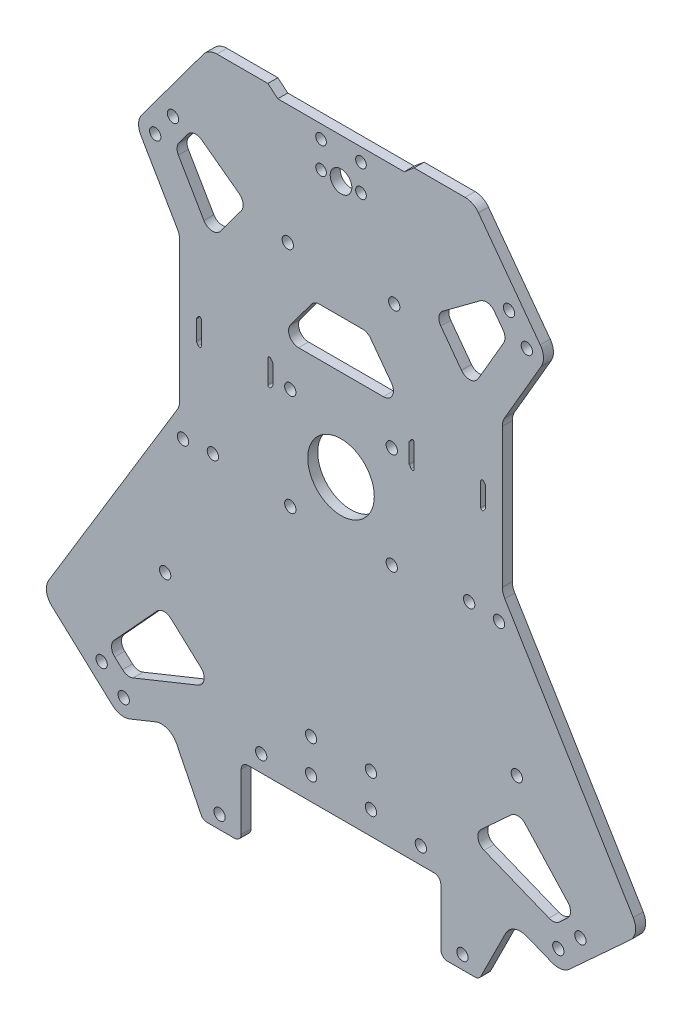
SolidWorks part; units mm, degrees
material "Thornel Mat VMA"
ref_plane "Front Plane" through (0, 0, 0) normal (0, 0, 1) x (1, 0, 0)
ref_plane "Top Plane" through (0, 0, 0) normal (0, 1, 0) x (1, 0, 0)
ref_plane "Right Plane" through (0, 0, 0) normal (1, 0, 0) x (0, 0, -1)
sketch "Sketch1" plane through (0, 0, 0) normal (0, 0, 1) x (1, 0, 0)
  line L0 (0, 0) -> (19, 0)
  line L1 (19, 0) -> (21.9794, 2.5)
  line L2 (21.9794, 2.5) -> (39.8216, 2.5)
  line L3 (39.8216, 2.5) -> (61.83, -27.2427)
  line L4 (61.83, -27.2427) -> (48.5, -50.146)
  line L5 (48.5, -50.146) -> (48.5, -94.8136)
  line L6 (48.5, -94.8136) -> (89.9615, -163.231)
  line L7 (89.9615, -163.231) -> (66.3721, -184.8537)
  line L8 (66.3721, -184.8537) -> (51.5362, -178.8624)
  line L9 (51.5362, -178.8624) -> (41.5, -199)
  line L10 (41.5, -199) -> (30, -199)
  line L11 (30, -199) -> (30, -178)
  line L12 (30, -178) -> (0, -178)
  line L14 (0, 0) -> (0, -178)
  circle A0 centre (6, -4) radius 1.6
  dimension "D20" = 3.2
  dimension "D2" = 2.5
  dimension "D3" = 140
  dimension "D4" = 113.3
  dimension "D5" = 126.5
  dimension "D6" = 37
  dimension "D7" = 30
  dimension "D8" = 26.5
  dimension "D9" = 41.5
  dimension "D10" = 48.5
  dimension "D11" = 80
  dimension "D12" = 178
  dimension "D13" = 32
  dimension "D14" = 115.5
  dimension "D15" = 16
  dimension "D16" = 94.5
  dimension "D17" = 22.5
  dimension "D18" = 116.491
  dimension "D19" = 21
  dimension "D21" = 19
  dimension "D22" = 4
  dimension "D23" = 6
extrude "Boss-Extrude1" add sketch "Sketch1" along normal blind 3 contours L14 L12 L11 L10 L9 L8 L7 L6 L5 L4 L3 L2 L1 L0
extrude "Cut-Extrude1" cut sketch "Sketch1<3>" along normal through all contours A0
sketch "Sketch1<3>" plane through (0, 0, 0) normal (0, 0, 1) x (1, 0, 0) same geometry as "Sketch1"
fillet "Fillet1" radius 5 7 edges at (39.8216, 2.5, 1.5) (51.5362, -178.8624, 1.5) (66.3721, -184.8537, 1.5) (89.9615, -163.231, 1.5) (48.5, -94.8136, 1.5) (48.5, -50.146, 1.5) (61.83, -27.2427, 1.5)
fillet "Fillet2" radius 2 3 edges at (30, -178, 1.5) (30, -199, 1.5) (41.5, -199, 1.5)
hole_wizard "M3 Clearance Hole2" positions "Sketch6" profile "Sketch7" hole size "M3" standard "ANSI Metric" end condition up to next
sketch "Sketch6" plane through (0, 0, 3) normal (0, 0, 1) x (1, 0, 0)
  line L0 (71.9537, -172.9547) -> (65.3192, -179.0361) construction
  line L2 (86.9389, -166.0016) -> (68.6977, -182.722) construction
  line L3 (71.9537, -172.9547) -> (77.851, -167.5491) construction
  line L7 (52.8498, -140.2738) -> (55.4731, -103.367) construction
  line L9 (52.8498, -140.2738) -> (77.851, -167.5491) construction
  line L11 (55.4731, -103.367) -> (47.4932, -102.7998) construction
  line L12 (47.4932, -102.7998) -> (38.5159, -102.1616) construction
  line L13 (47.4932, -102.7998) -> (51.7693, -100.2084) construction
  line L14 (49.2239, -96.0081) -> (87.8365, -159.7244) construction
  line L15 (50.5, -20.3369) -> (55.8534, -27.5716) construction
  line L17 (41.3207, 0.4741) -> (59.8727, -24.5975) construction
  line L18 (50.5, -20.3369) -> (45.7414, -13.9061) construction
  line L20 (45.7414, -13.9061) -> (15.9987, -35.9145) construction
  point P0 (65.3192, -179.0361)
  point P3 (71.9537, -172.9547)
  point P23 (52.8498, -140.2738)
  point P34 (47.4932, -102.7998)
  point P36 (38.5159, -102.1616)
  point P48 (55.8534, -27.5716)
  point P51 (50.5, -20.3369)
  point P66 (15.9987, -35.9145)
  dimension "D1" = 9
  dimension "D2" = 37
  dimension "D3" = 8
  dimension "D4" = 5
sketch "Sketch7" plane through (65.3192, -179.0361, 3) normal (1, 0, 0) x (0, -1, 0)
  line L0 (0, 0) -> (0, 3.001)
  line L1 (0, 3.001) -> (1.7, 3.001)
  line L2 (1.7, 3.001) -> (1.7, 0)
  line L5 (1.7, 0) -> (0, 0)
  line L11 (0, -6.35) -> (0, 107.95) construction
  dimension "Thru Hole Dia." = 3.4
  dimension "Thru Hole Depth" = 3.001
hole_wizard "M3 Clearance Hole3" positions "Sketch8" profile "Sketch9" hole size "M3" standard "ANSI Metric" end condition up to next
sketch "Sketch8" plane through (0, 0, 3) normal (0, 0, 1) x (1, 0, 0)
  line L0 (9, -171) -> (9, -178) construction
  line L1 (28, -178) -> (0, -178) construction
  line L3 (24, -173) -> (24, -178) construction
  line L5 (9, -171) -> (9, -161) construction
  line L6 (30, -197) -> (30, -180) construction
  line L7 (40.2621, -199) -> (32, -199) construction
  line L8 (0, 0) -> (0, -178) construction
  point P0 (9, -171)
  point P2 (24, -173)
  point P15 (9, -161)
  point P19 (36.5, -195)
  dimension "D1" = 5
  dimension "D2" = 7
  dimension "D3" = 9
  dimension "D4" = 24
  dimension "D5" = 10
  dimension "D6" = 6.5
  dimension "D7" = 4
sketch "Sketch9" plane through (9, -171, 3) normal (1, 0, 0) x (0, -1, 0)
  line L0 (0, 0) -> (0, 3.001)
  line L1 (0, 3.001) -> (1.7, 3.001)
  line L2 (1.7, 3.001) -> (1.7, 0)
  line L5 (1.7, 0) -> (0, 0)
  line L11 (0, -6.35) -> (0, 107.95) construction
  dimension "Thru Hole Dia." = 3.4
  dimension "Thru Hole Depth" = 3.001
mirror "Mirror2" about plane through (0, 0, 3) normal (1, 0, 0) of "M3 Clearance Hole3", "Cut-Extrude1", "Boss-Extrude1", "Fillet1", "Fillet2", "M3 Clearance Hole2"
hole_wizard "M3 Clearance Hole4" positions "Sketch10" profile "Sketch11" hole size "M3" standard "ANSI Metric" end condition up to next
sketch "Sketch10" plane through (0, 0, 3) normal (0, 0, 1) x (1, 0, 0)
  line L1 (15.25, -104.25) -> (-15.25, -104.25) construction
  line L4 (15.25, -73.75) -> (15.25, -104.25) construction
  line L7 (-15.25, -73.75) -> (-15.25, -104.25) construction
  line L9 (15.25, -73.75) -> (-15.25, -73.75) construction
  line L14 (0, 0) -> (0, -178) construction
  line L15 (28, -178) -> (-28, -178) construction
  line L17 (15.25, -104.25) -> (-15.25, -73.75) construction
  point P0 (15.25, -104.25)
  point P7 (-15.25, -104.25)
  point P17 (15.25, -73.75)
  point P19 (-15.25, -73.75)
  point P54 (0, -89)
  dimension "D2" = 30.5
sketch "Sketch11" plane through (15.25, -104.25, 3) normal (1, 0, 0) x (0, -1, 0)
  line L0 (0, 0) -> (0, 3)
  line L1 (0, 3) -> (1.7, 3)
  line L2 (1.7, 3) -> (1.7, 0)
  line L5 (1.7, 0) -> (0, 0)
  line L11 (0, -6.35) -> (0, 107.95) construction
  dimension "Thru Hole Dia." = 3.4
  dimension "Thru Hole Depth" = 3
sketch "Sketch12" plane through (0, 0, 3) normal (0, 0, 1) x (1, 0, 0)
  line L0 (0, 0) -> (0, -50000) construction
  line L7 (-41.8818, -22.1395) -> (-30.6278, -30.467)
  line L12 (41.216, -42.7812) -> (48.8836, -29.6069)
  line L19 (48.7024, -26.3134) -> (46.0779, -22.7666)
  line L20 (41.8818, -22.1395) -> (30.6278, -30.467)
  line L21 (30.0007, -34.663) -> (36.2116, -43.0566)
  line L22 (41.3207, 0.4741) -> (59.8727, -24.5975) construction
  line L23 (60.1748, -30.0867) -> (49.1786, -48.98) construction
  line L24 (48.8836, -29.6069) -> (57.5264, -34.6371) construction
  line L25 (48.7024, -26.3134) -> (56.7409, -20.3652) construction
  line L26 (-48.7024, -26.3134) -> (-46.0779, -22.7666)
  line L27 (-41.216, -42.7812) -> (-48.8836, -29.6069)
  line L28 (-30.0007, -34.663) -> (-36.2116, -43.0566)
  line L29 (65.6616, -171.9396) -> (68.0078, -169.7889)
  line L30 (68.1922, -165.5503) -> (55.3537, -151.5441)
  line L31 (51.1151, -151.3597) -> (42.0882, -159.634)
  line L32 (42.992, -164.6272) -> (62.5111, -172.5098)
  line L33 (63.4469, -183.6723) -> (55.8219, -180.5931) construction
  line L34 (86.9389, -166.0016) -> (68.6977, -182.722) construction
  line L35 (65.6616, -171.9396) -> (72.4187, -179.3112) construction
  line L36 (62.5111, -172.5098) -> (58.7665, -181.7822) construction
  line L37 (-51.1151, -151.3597) -> (-42.0882, -159.634)
  line L38 (-68.1922, -165.5503) -> (-55.3537, -151.5441)
  line L39 (-65.6616, -171.9396) -> (-68.0078, -169.7889)
  line L40 (-42.992, -164.6272) -> (-62.5111, -172.5098)
  line L43 (6, -12) -> (-6, -12) construction
  line L54 (6.4879, -47.2107) -> (-6.4879, -47.2107)
  line L55 (-8.8994, -48.4262) -> (-15.1665, -56.8957)
  line L56 (-12.7549, -61.6801) -> (12.7549, -61.6801)
  line L57 (15.1665, -56.8957) -> (8.8994, -48.4262)
  line L58 (28.2162, -32.2515) -> (8, -47.2107) construction
  line L59 (18.7068, -61.6801) -> (38.9231, -46.7209) construction
  line L64 (15.25, -104.25) -> (-15.25, -73.75) construction
  line L72 (42, -75.9559) -> (42, -68.9559)
  line L73 (42.9, -68.6559) -> (43.4, -69.3226)
  line L74 (43.5, -69.6226) -> (43.5, -75.2893)
  line L75 (43.4, -75.5893) -> (42.9, -76.2559)
  line L76 (48.5, -72.4559) -> (43.5, -72.4559) construction
  line L77 (22, -75.9559) -> (22, -68.9559)
  line L78 (21.1, -68.6559) -> (20.6, -69.3226)
  line L79 (20.5, -69.6226) -> (20.5, -75.2893)
  line L80 (20.6, -75.5893) -> (21.1, -76.2559)
  line L81 (42, -72.4559) -> (22, -72.4559) construction
  line L82 (48.5, -51.4951) -> (48.5, -93.4168) construction
  line L83 (-43.4, -75.5893) -> (-42.9, -76.2559)
  line L84 (-43.5, -69.6226) -> (-43.5, -75.2893)
  line L85 (-42.9, -68.6559) -> (-43.4, -69.3226)
  line L86 (-42, -75.9559) -> (-42, -68.9559)
  line L87 (-20.6, -75.5893) -> (-21.1, -76.2559)
  line L88 (-20.5, -69.6226) -> (-20.5, -75.2893)
  line L89 (-21.1, -68.6559) -> (-20.6, -69.3226)
  line L90 (-22, -75.9559) -> (-22, -68.9559)
  arc A8 (-46.0779, -22.7666) -> (-41.8818, -22.1395) centre (-43.6663, -24.551) cw
  arc A13 (6.4879, -47.2107) -> (8.8994, -48.4262) centre (6.4879, -50.2107) cw
  arc A15 (41.216, -42.7812) -> (36.2116, -43.0566) centre (38.6232, -41.2721) cw
  arc A16 (30.6278, -30.467) -> (30.0007, -34.663) centre (32.4123, -32.8786) ccw
  arc A17 (46.0779, -22.7666) -> (41.8818, -22.1395) centre (43.6663, -24.551) ccw
  arc A18 (48.8836, -29.6069) -> (48.7024, -26.3134) centre (46.2908, -28.0979) ccw
  arc A19 (-48.8836, -29.6069) -> (-48.7024, -26.3134) centre (-46.2908, -28.0979) cw
  arc A20 (-41.216, -42.7812) -> (-36.2116, -43.0566) centre (-38.6232, -41.2721) ccw
  arc A21 (-30.6278, -30.467) -> (-30.0007, -34.663) centre (-32.4123, -32.8786) cw
  arc A22 (65.6616, -171.9396) -> (62.5111, -172.5098) centre (63.6344, -169.7281) cw
  arc A23 (68.0078, -169.7889) -> (68.1922, -165.5503) centre (65.9807, -167.5774) ccw
  arc A24 (55.3537, -151.5441) -> (51.1151, -151.3597) centre (53.1422, -153.5712) ccw
  arc A25 (42.0882, -159.634) -> (42.992, -164.6272) centre (44.1153, -161.8455) ccw
  arc A26 (-55.3537, -151.5441) -> (-51.1151, -151.3597) centre (-53.1422, -153.5712) cw
  arc A27 (-68.0078, -169.7889) -> (-68.1922, -165.5503) centre (-65.9807, -167.5774) cw
  arc A28 (-65.6616, -171.9396) -> (-62.5111, -172.5098) centre (-63.6344, -169.7281) ccw
  arc A29 (-42.0882, -159.634) -> (-42.992, -164.6272) centre (-44.1153, -161.8455) cw
  circle A37 centre (0, -12) radius 3.25
  circle A38 centre (6, -12) radius 1.6
  circle A39 centre (-6, -12) radius 1.6
  arc A40 (-6.4879, -47.2107) -> (-8.8994, -48.4262) centre (-6.4879, -50.2107) ccw
  arc A41 (-15.1665, -56.8957) -> (-12.7549, -61.6801) centre (-12.7549, -58.6801) ccw
  arc A42 (12.7549, -61.6801) -> (15.1665, -56.8957) centre (12.7549, -58.6801) ccw
  arc A47 (42, -75.9559) -> (42.9, -76.2559) centre (42.5, -75.9559) ccw
  arc A48 (42, -68.9559) -> (42.9, -68.6559) centre (42.5, -68.9559) cw
  arc A49 (43.4, -69.3226) -> (43.5, -69.6226) centre (43, -69.6226) cw
  arc A50 (43.5, -75.2893) -> (43.4, -75.5893) centre (43, -75.2893) cw
  arc A51 (20.5, -75.2893) -> (20.6, -75.5893) centre (21, -75.2893) ccw
  arc A52 (20.6, -69.3226) -> (20.5, -69.6226) centre (21, -69.6226) ccw
  arc A53 (22, -68.9559) -> (21.1, -68.6559) centre (21.5, -68.9559) ccw
  arc A54 (22, -75.9559) -> (21.1, -76.2559) centre (21.5, -75.9559) cw
  arc A55 (-42, -75.9559) -> (-42.9, -76.2559) centre (-42.5, -75.9559) cw
  arc A56 (-43.5, -75.2893) -> (-43.4, -75.5893) centre (-43, -75.2893) ccw
  arc A57 (-43.4, -69.3226) -> (-43.5, -69.6226) centre (-43, -69.6226) ccw
  arc A58 (-42, -68.9559) -> (-42.9, -68.6559) centre (-42.5, -68.9559) ccw
  arc A59 (-22, -75.9559) -> (-21.1, -76.2559) centre (-21.5, -75.9559) ccw
  arc A60 (-20.5, -75.2893) -> (-20.6, -75.5893) centre (-21, -75.2893) cw
  arc A61 (-20.6, -69.3226) -> (-20.5, -69.6226) centre (-21, -69.6226) cw
  arc A62 (-22, -68.9559) -> (-21.1, -68.6559) centre (-21.5, -68.9559) cw
  circle A63 centre (0, -89) radius 10
  point P6 (0, -47.2107)
  point P22 (-8, -47.2107)
  point P54 (38.9231, -46.7209)
  point P57 (28.2162, -32.2515)
  point P60 (44.2934, -20.355)
  point P89 (70.2193, -167.7618)
  point P92 (53.3266, -149.3326)
  point P95 (38.5832, -162.8468)
  dimension "D3" = 12
  dimension "D7" = 20
  dimension "D4" = 3.2
  dimension "D11" = 3
  dimension "D15" = 3
  dimension "D2" = 6.5
  dimension "D6" = 3
  dimension "D23" = 0.5
  dimension "D5" = 16
  dimension "D9" = 20
  dimension "D10" = 18
  dimension "D12" = 10
  dimension "D13" = 25
  dimension "D14" = 20
  dimension "D16" = 12
  dimension "D17" = 20
  dimension "D18" = 5.6667
  dimension "D19" = 7
  dimension "D20" = 1.5
  dimension "D21" = 1.5
  dimension "D22" = 5
extrude "Cut-Extrude2" cut sketch "Sketch12" against normal up to next
